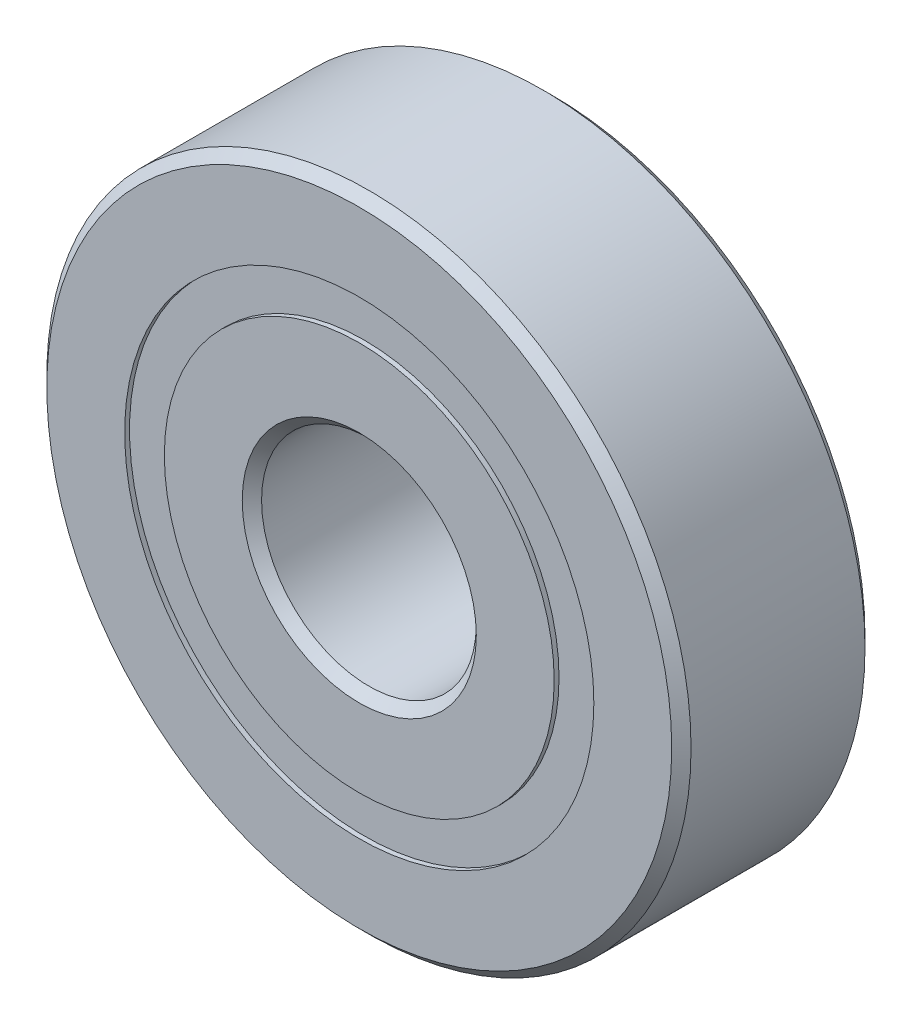
SolidWorks part; units mm, degrees
ref_plane "Front Plane" through (0, 0, 0) normal (0, 0, 1) x (1, 0, 0)
ref_plane "Top Plane" through (0, 0, 0) normal (0, 1, 0) x (1, 0, 0)
ref_plane "Right Plane" through (0, 0, 0) normal (1, 0, 0) x (0, 0, -1)
sketch "Sketch1" plane through (0, 0, 0) normal (1, 0, 0) x (0, 0, -1)
  line L0 (-4.5, 0) -> (4.5, 0) construction
  line L1 (0, 15) -> (0, -15) construction
  line L2 (4.05, 15) -> (-4.05, 15)
  line L3 (-4.05, 15) -> (-4.5, 14.55)
  line L4 (-4.5, 14.55) -> (-4.5, 10.9231)
  line L5 (-4.5, 10.9231) -> (-2, 10.9231)
  line L6 (4.5, 10.9231) -> (2, 10.9231)
  line L7 (4.5, 14.55) -> (4.5, 10.9231)
  line L8 (4.05, 15) -> (4.5, 14.55)
  line L9 (0, 15) -> (0, 10) construction
  line L10 (0, 10) -> (0, 5) construction
  arc A0 (-2, 10.9231) -> (2, 10.9231) centre (0, 10) cw
  point P14 (0, 5)
  dimension "Width" = 9
  dimension "OD" = 30
  dimension "D1" = 45
  dimension "D2" = 0.45
  dimension "Shaft Dia" = 10
  dimension "D3" = 4
  dimension "D4" = 0.9231
revolve "Revolve1" add sketch "Sketch1" angle 360 about L0
sketch "Sketch3" plane through (0, 0, 0) normal (1, 0, 0) x (0, 0, -1)
  line L0 (-4.5, 9.0769) -> (-2, 9.0769)
  line L1 (0, 15) -> (0, -15) construction
  line L2 (-4.5, 14.55) -> (-4.5, 10.9231) construction
  line L3 (-4.5, 9.0769) -> (-4.5, 5.45)
  line L4 (-4.05, 15) -> (-4.5, 14.55) construction
  line L5 (-4.5, 5.45) -> (-4.05, 5)
  line L6 (-4.05, 5) -> (4.05, 5)
  line L7 (4.05, 15) -> (4.05, -15) construction
  line L8 (4.05, 5) -> (4.5, 5.45)
  line L9 (4.5, -14.55) -> (4.5, 14.55) construction
  line L10 (4.5, 5.45) -> (4.5, 9.0769)
  line L11 (4.5, 9.0769) -> (2, 9.0769)
  line L13 (4.05, 15) -> (4.5, 14.55) construction
  arc A0 (2, 10.9231) -> (-2, 10.9231) centre (0, 10) ccw construction
  arc A1 (2, 9.0769) -> (-2, 9.0769) centre (0, 10) cw
revolve "Revolve3" add sketch "Sketch3" angle 360 about L0
sketch "Sketch4" plane through (0, 0, 0) normal (1, 0, 0) x (0, 0, -1)
  line L0 (-2.2027, 10) -> (2.2027, 10)
  arc A2 (-2.2027, 10) -> (2.2027, 10) centre (0, 10) cw
  arc A3 (2, 10.9231) -> (-2, 10.9231) centre (0, 10) ccw construction
revolve "Revolve4" add sketch "Sketch4" angle 360 about L0
ref_axis "Axis1" through (0, 0, -4.5) along (0, 0, 1)
pattern_circular "CirPattern1" count 12 every 30 about axis through (0, 0, -4.5) along (0, 0, 1) of bodies 104
sketch "Sketch5" plane through (0, 0, 0) normal (1, 0, 0) x (0, 0, -1)
  line L0 (-4.5, 10.9231) -> (-2, 10.9231) construction
  line L1 (-4.275, 10.9231) -> (-2.2027, 10.9231)
  line L2 (-4.275, 10.9231) -> (-4.275, 9.0769)
  line L3 (-4.275, 9.0769) -> (-2.2027, 9.0769)
  line L4 (-2.2027, 10.9231) -> (-2.2027, 9.0769)
  line L5 (-4.5, 9.0769) -> (-2, 9.0769) construction
  line L6 (4.5, 10.9231) -> (2, 10.9231) construction
  line L7 (4.275, 10.9231) -> (2.2027, 10.9231)
  line L8 (4.275, 10.9231) -> (4.275, 9.0769)
  line L9 (4.275, 9.0769) -> (2.2027, 9.0769)
  line L10 (2.2027, 10.9231) -> (2.2027, 9.0769)
  line L11 (4.5, 9.0769) -> (2, 9.0769) construction
  line L12 (-4.05, 15) -> (-4.5, 14.55) construction
  point P18 (-4.275, 14.775)
revolve "Revolve5" add sketch "Sketch5" angle 360 about L0
equation "\"D2@Sketch1\" = \"Width@Sketch1\"*.05"
equation "\"D3@Sketch1\" = \"Width@Sketch1\"/2.25"
equation "\"D4@Sketch1\" = (((\"OD@Sketch1\"-\"Width@Sketch1\")/2)/3.25)/3.5"
equation "\"D2@CirPattern1\" = 360/\"Balls@CirPattern1\""
